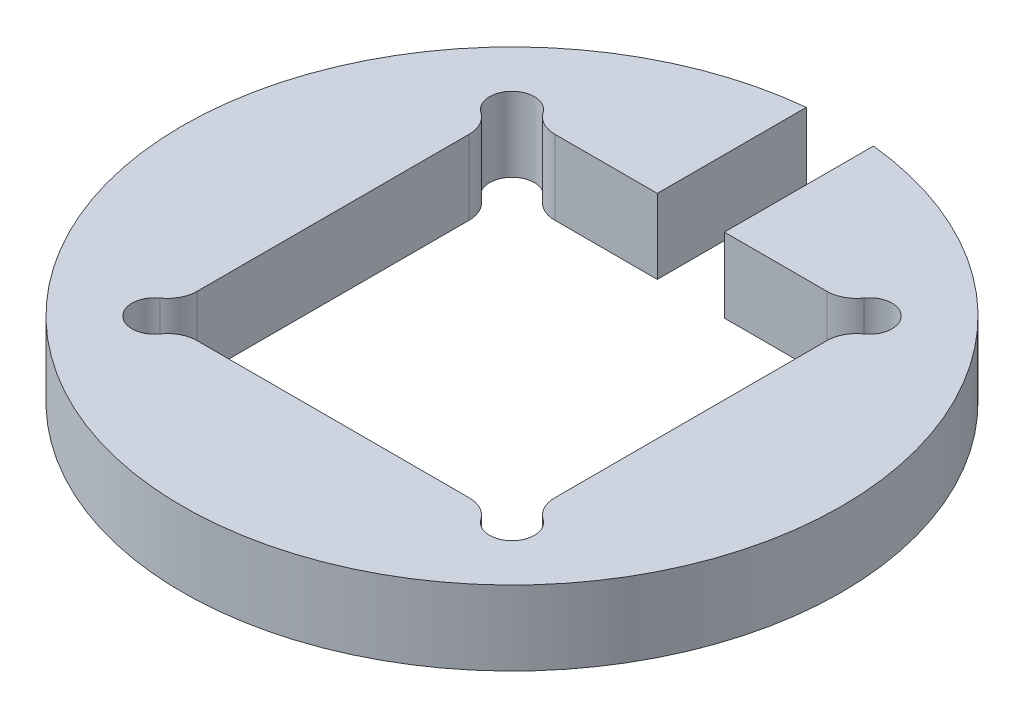
SolidWorks part; units mm, degrees
ref_plane "Front Plane" through (0, 0, 0) normal (0, 0, 1) x (1, 0, 0)
ref_plane "Top Plane" through (0, 0, 0) normal (0, 1, 0) x (1, 0, 0)
ref_plane "Right Plane" through (0, 0, 0) normal (1, 0, 0) x (0, 0, -1)
sketch "Sketch1" plane through (0, 0, 0) normal (0, 1, 0) x (1, 0, 0)
  line L0 (0, 0) -> (0, 24)
  line L1 (0, 24) -> (9.75, 24)
  line L2 (9.75, 24) -> (9.75, 34)
  line L3 (0, 0) -> (24, 0)
  line L4 (24, 0) -> (24, 24)
  line L5 (24, 24) -> (14.25, 24)
  line L6 (14.25, 24) -> (14.25, 34)
  line L7 (0, 12) -> (24, 12) construction
  arc A2 (14.25, 34) -> (9.75, 34) centre (12, 12) cw
  arc A3 (22.5, 24) -> (24, 22.5) centre (24, 24) cw
  arc A4 (24, 1.5) -> (22.5, 0) centre (24, 0) cw
  arc A5 (1.5, 0) -> (0, 1.5) centre (0, 0) cw
  arc A6 (1.5, 24) -> (0, 22.5) centre (0, 24) ccw
  dimension "D1" = 24
  dimension "D7" = 1.5
  dimension "D5" = 1.5
  dimension "D8" = 1.5
  dimension "D9" = 1.5
  dimension "D2" = 24
  dimension "D3" = 4.5
  dimension "D4" = 10
extrude "Boss-Extrude1" add sketch "Sketch1" along normal blind 5 contours A6 L1 L2 A2 L6 L5 A3 L4 A4 L3 A5 L0 region at (-1.5024, 0, 1.5024)
fillet "Fillet1" radius 2 8 edges at (22.5, 2.5, 0) (24, 2.5, -1.5) (24, 2.5, -22.5) (0, 2.5, -1.5) (1.5, 2.5, 0) (0, 2.5, -22.5) (22.5, 2.5, -24) (1.5, 2.5, -24)
